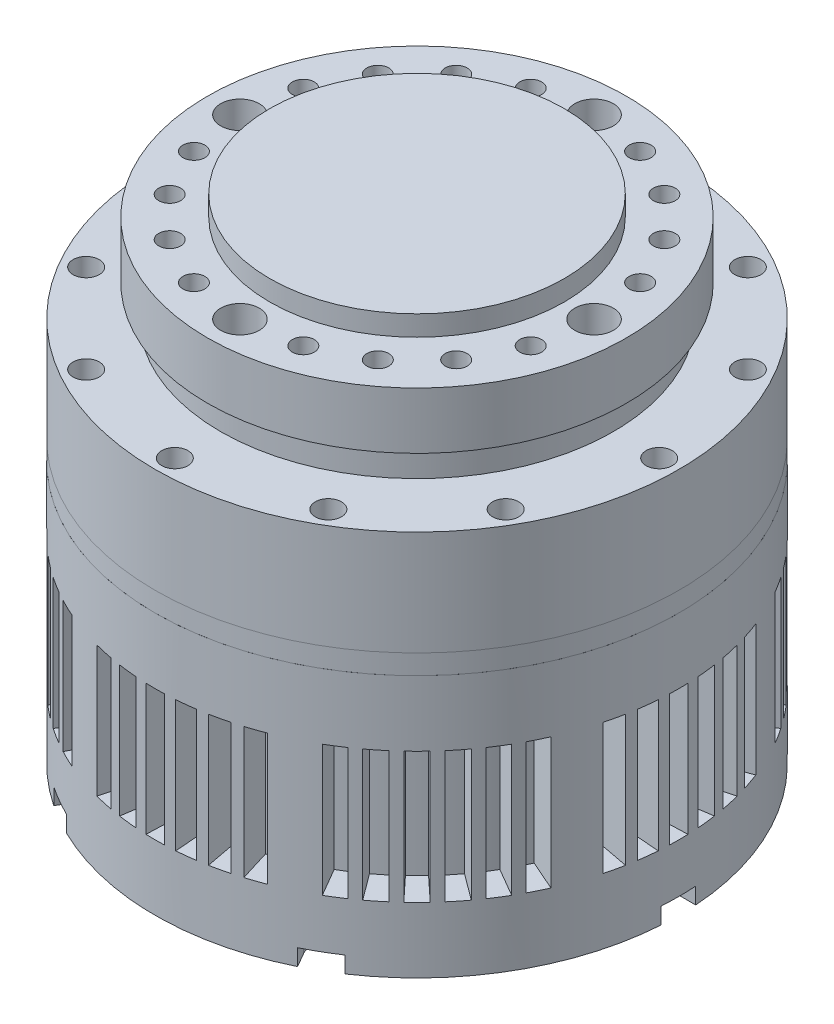
SolidWorks part; units mm, degrees
ref_plane "Front Plane" through (0, 0, 0) normal (0, 0, 1) x (1, 0, 0)
ref_plane "Top Plane" through (0, 0, 0) normal (0, 1, 0) x (1, 0, 0)
ref_plane "Right Plane" through (0, 0, 0) normal (1, 0, 0) x (0, 0, -1)
sketch "Sketch1" plane through (0, 0, 0) normal (0, 1, 0) x (1, 0, 0)
  circle A0 centre (0, 0) radius 40
  dimension "D1" = 80
extrude "Boss-Extrude1" add sketch "Sketch1" along normal blind 16 contours A0
sketch "Sketch2" plane through (0, 16, 0) normal (0, 1, 0) x (1, 0, 0)
  circle A0 centre (0, 37) radius 2
  dimension "D1" = 4
  dimension "D2" = 37
extrude "Cut-Extrude1" cut sketch "Sketch2" against normal blind 5
pattern_circular "CirPattern1" count 12 over 360 about axis through (0, 16, 0) along (0, 1, 0) of "Cut-Extrude1"
sketch "Sketch3" plane through (0, 0, 0) normal (0, -1, 0) x (1, 0, 0)
  circle A0 centre (0, 0) radius 40
  circle A1 centre (0, 0) radius 40 construction
extrude "Boss-Extrude2" add sketch "Sketch3" along normal blind 3 separate body
sketch "Sketch4" plane through (0, -3, 0) normal (0, -1, 0) x (1, 0, 0)
  circle A0 centre (0, 0) radius 40
  circle A1 centre (0, 0) radius 40 construction
extrude "Boss-Extrude3" add sketch "Sketch4" along normal blind 40 separate body
sketch "Sketch5" plane through (0, -43, 0) normal (0, -1, 0) x (1, 0, 0)
  line L0 (-10.2297, 38.6698) -> (-8.951, 33.8361)
  line L1 (-6.5128, 34.3887) -> (-7.4432, 39.3014)
  line L2 (-5.1323, 34.6217) -> (-5.8655, 39.5676)
  line L3 (-2.6478, 34.8997) -> (-3.0261, 39.8854)
  line L4 (-1.4286, 39.9745) -> (-1.25, 34.9777)
  line L5 (1.4286, 39.9745) -> (1.25, 34.9777)
  line L6 (2.6478, 34.8997) -> (3.0261, 39.8854)
  line L7 (5.1323, 34.6217) -> (5.8655, 39.5676)
  line L8 (7.4432, 39.3014) -> (6.5128, 34.3887)
  line L9 (10.2297, 38.6698) -> (8.951, 33.8361)
  line L10 (14.4669, 37.2922) -> (12.6585, 32.6307)
  line L11 (11.768, 38.2298) -> (10.297, 33.451)
  line L12 (-6.978, 36.845) -> (-5.4989, 37.0946) construction
  line L13 (-2.837, 37.3925) -> (-1.3393, 37.4761) construction
  line L14 (1.3393, 37.4761) -> (2.837, 37.3925) construction
  line L15 (5.4989, 37.0946) -> (6.978, 36.845) construction
  line L16 (9.5903, 36.2529) -> (11.0325, 35.8404) construction
  line L17 (-9.5903, 36.2529) -> (-6.978, 36.845) construction
  line L18 (-5.4989, 37.0946) -> (-2.837, 37.3925) construction
  line L19 (-1.3393, 37.4761) -> (1.3393, 37.4761) construction
  line L20 (2.837, 37.3925) -> (5.4989, 37.0946) construction
  line L21 (6.978, 36.845) -> (9.5903, 36.2529) construction
  line L22 (11.0325, 35.8404) -> (13.5627, 34.9614) construction
  line L23 (28.7562, 44.6999) -> (-40.4872, 34.4353) construction
  line L24 (-5.8655, 39.5676) -> (0, 0) construction
  arc A0 (12.6585, 32.6307) -> (10.297, 33.451) centre (0, 0) ccw
  circle A1 centre (0, 0) radius 40 construction
  arc A3 (14.4669, 37.2922) -> (11.768, 38.2298) centre (0, 0) ccw
  arc A5 (-3.0261, 39.8854) -> (-5.8655, 39.5676) centre (0, 0) ccw
  arc A6 (1.4286, 39.9745) -> (-1.4286, 39.9745) centre (0, 0) ccw
  arc A7 (5.8655, 39.5676) -> (3.0261, 39.8854) centre (0, 0) ccw
  arc A8 (10.2297, 38.6698) -> (7.4432, 39.3014) centre (0, 0) ccw
  arc A9 (8.951, 33.8361) -> (6.5128, 34.3887) centre (0, 0) ccw
  arc A10 (5.1323, 34.6217) -> (2.6478, 34.8997) centre (0, 0) ccw
  arc A11 (1.25, 34.9777) -> (-1.25, 34.9777) centre (0, 0) ccw
  arc A12 (-2.6478, 34.8997) -> (-5.1323, 34.6217) centre (0, 0) ccw
  arc A13 (-6.5128, 34.3887) -> (-8.951, 33.8361) centre (0, 0) ccw
  arc A14 (-7.4432, 39.3014) -> (-5.8655, 39.5676) centre (0, 0) cw construction
  arc A15 (-1.4286, 39.9745) -> (-3.0261, 39.8854) centre (0, 0) ccw construction
  arc A16 (3.0261, 39.8854) -> (1.4286, 39.9745) centre (0, 0) ccw construction
  arc A17 (7.4432, 39.3014) -> (5.8655, 39.5676) centre (0, 0) ccw construction
  arc A18 (11.768, 38.2298) -> (10.2297, 38.6698) centre (0, 0) ccw construction
  arc A19 (-7.4432, 39.3014) -> (-10.2297, 38.6698) centre (0, 0) ccw
  point P15 (-5.8655, 39.5676)
  point P50 (0, 35)
  dimension "D1" = 5
  dimension "D2" = 2.5
  dimension "D3" = 70
  dimension "D4" = 1.5
sketch "Sketch6" plane through (0, 16, 0) normal (0, 1, 0) x (1, 0, 0)
  circle A0 centre (0, 0) radius 40 construction
  circle A1 centre (0, 0) radius 30
  dimension "D1" = 80
  dimension "D2" = 10
extrude "Boss-Extrude4" add sketch "Sketch6" along normal blind 4.75 separate body
sketch "Sketch8" plane through (0, 20.75, 0) normal (0, 1, 0) x (1, 0, 0)
  circle A0 centre (0, 0) radius 32
  dimension "D1" = 64
extrude "Boss-Extrude5" add sketch "Sketch8" along normal blind 8.65 separate body
sketch "Sketch9" plane through (0, 29.4, 0) normal (0, 1, 0) x (1, 0, 0)
  circle A0 centre (0, 0) radius 22.5
  dimension "D1" = 45
extrude "Boss-Extrude6" add sketch "Sketch9" along normal blind 3.1
sketch "Sketch10" plane through (0, 29.4, 0) normal (0, 1, 0) x (1, 0, 0)
  circle A40 centre (0, 27.05) radius 2.95
  dimension "D1" = 27.05
  dimension "D2" = 5.9
extrude "Cut-Extrude5" cut sketch "Sketch10" against normal blind 7
pattern_circular "CirPattern3" count 4 over 360 about axis through (0, 32.5, 0) along (0, 1, 0) of "Cut-Extrude5"
sketch "Sketch14" plane through (0, 29.4, 0) normal (0, 1, 0) x (1, 0, 0)
  line L0 (25.7261, 8.3589) -> (25.7261, 0) construction
  line L1 (25.7261, 0) -> (0, 0) construction
  line L2 (0, 0) -> (25.7261, 8.3589) construction
  circle A0 centre (25.7261, 8.3589) radius 1.675
  circle A1 centre (0, 0) radius 27.05 construction
  dimension "D2" = 3.35
  dimension "D1" = 18
extrude "Cut-Extrude6" cut sketch "Sketch14" against normal blind 7
pattern_circular "CirPattern4" count 20 over 360 about axis through (0, 32.5, 0) along (0, 1, 0) skipping 4, 9, 14, 19 of "Cut-Extrude6"
sketch "Sketch16" plane through (0, -43, 0) normal (0, -1, 0) x (1, 0, 0)
  line L0 (-18.6667, 32.3316) -> (18.6667, 32.3316) construction
  line L1 (-16, 32.3316) -> (16, 32.3316) construction
  line L2 (-18.6667, 32.3316) -> (0, 0) construction
  line L3 (0, 0) -> (18.6667, 32.3316) construction
  line L4 (20.9761, 30.9983) -> (22.2649, 33.2306)
  line L5 (16.3573, 33.6649) -> (17.6461, 35.8973)
  circle A0 centre (-18.6667, 32.3316) radius 2.6667 construction
  circle A1 centre (0, 0) radius 40 construction
  arc A2 (16.3573, 33.6649) -> (20.9761, 30.9983) centre (18.6667, 32.3316) ccw construction
  arc A3 (16.3573, 33.6649) -> (20.9761, 30.9983) centre (18.6667, 32.3316) ccw
  arc A4 (17.6461, 35.8973) -> (22.2649, 33.2306) centre (0, 0) cw
  point P8 (0, 32.3316)
  dimension "D3" = 5.3333
  dimension "D1" = 32
  dimension "D2" = 60
  dimension "D4" = 37.3333
extrude "Cut-Extrude8" cut sketch "Sketch16" against normal blind 2.5
pattern_circular "CirPattern5" count 6 over 360 about axis through (0, -43, 0) along (0, -1, 0) of "Cut-Extrude8"
extrude "Cut-Extrude9" cut sketch "Sketch5" against normal blind 20 from offset 10 offset against normal yes
pattern_circular "CirPattern6" count 8 over 360 about axis through (0, 16, 0) along (0, 1, 0) of "Cut-Extrude9"
sketch "Sketch17" plane through (0, 29.4, 0) normal (0, 1, 0) x (1, 0, 0)
  circle A0 centre (0, 0) radius 27.05 construction
  circle A1 centre (15.8996, 21.8839) radius 1.675
  circle A2 centre (15.8996, 21.8839) radius 1.675 construction
equation "\"small black ring h\"= 4.75mm"
equation "\"D1@Boss-Extrude4\"=\"small black ring h\""
equation "\"D1@Boss-Extrude5\"=13.4-\"small black ring h\""
